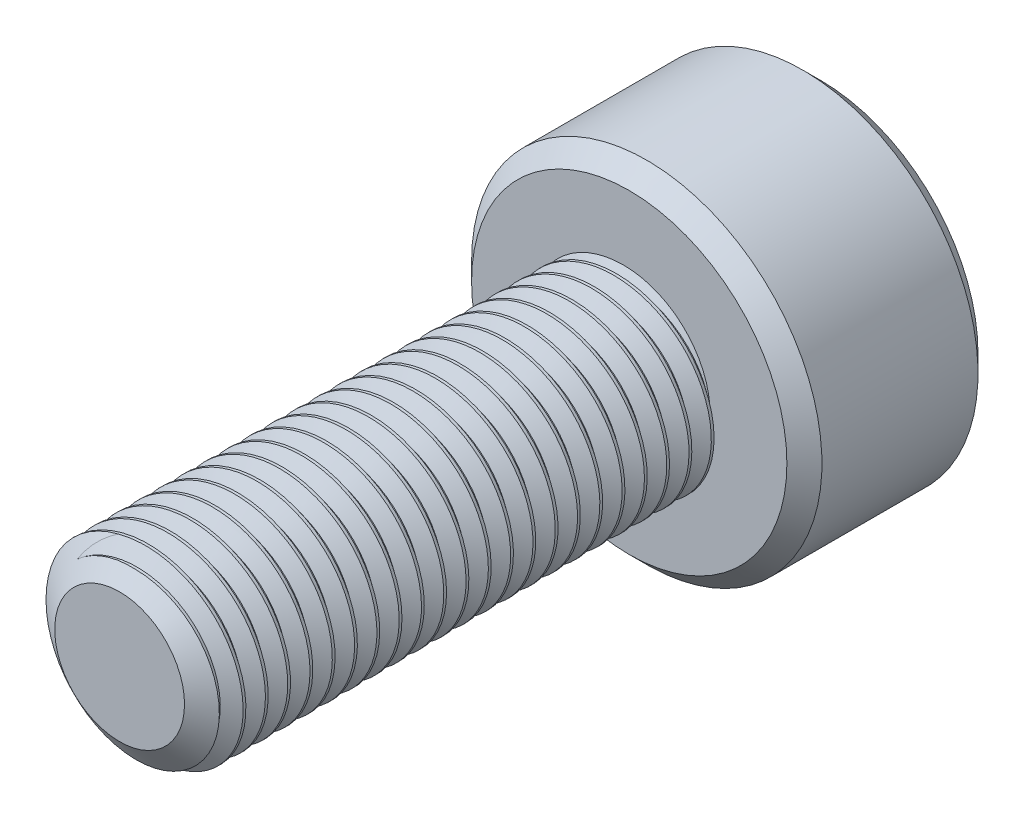
SolidWorks part; units mm, degrees
other "DetailItem1"
ref_plane "Front Plane" through (0, 0, 0) normal (0, 0, 1) x (1, 0, 0)
ref_plane "Top Plane" through (0, 0, 0) normal (0, 1, 0) x (1, 0, 0)
ref_plane "Right Plane" through (0, 0, 0) normal (1, 0, 0) x (0, 0, -1)
sketch "Sketch1" plane through (0, 0, 0) normal (0, 0, 1) x (1, 0, 0)
  circle A0 centre (0, 0) radius 1.5
  dimension "OD" = 3
extrude "Extrude1" add sketch "Sketch1" against normal blind 8
sketch "Sketch2" plane through (0, 0, 0) normal (0, 0, 1) x (1, 0, 0)
  circle A0 centre (0, 0) radius 1.5 construction
  circle A1 centre (0, 0) radius 1.5
curve "Helix/Spiral1" pitch 0.35 height 8.35 radius 1.5 centre (0, 0, 0) axis (0, 0, -1) start towards (0, 1, 0) parameters "pitch"=0.35
sketch "Sketch3" plane through (0, 0, 0) normal (1, 0, 0) x (0, 0, -1)
  line L0 (-0.3062, 1.5) -> (-0.175, 1.2727)
  line L1 (-0.175, 1.2727) -> (-0.1313, 1.2727)
  line L2 (-0.1313, 1.2727) -> (0, 1.5)
  line L3 (-0.3062, 1.5) -> (0, 1.5)
  line L4 (-0.1531, 1.5) -> (-0.1531, 1.2727) construction
  line L5 (-0.2406, 1.3863) -> (-0.0656, 1.3863) construction
  line L6 (0, 1.5) -> (0, -1.5) construction
  dimension "D1" = 0.0437
  dimension "D2" = 0.175
  dimension "D3" = 60
sweep "Cut-Sweep1" cut profiles "Sketch3" path "Helix/Spiral1" align with end faces yes
sketch "Sketch4" plane through (0, 0, 0) normal (1, 0, 0) x (0, 0, -1)
  line L0 (0.337, 1.5) -> (0, 1.0187)
  line L1 (0, 1.0187) -> (0, 1.5)
  line L2 (0.337, 1.5) -> (0, 1.5)
  line L3 (-0.3062, 1.5) -> (0, 1.5) construction
  line L4 (0, 0) -> (7.0209, 0) construction
  dimension "D1" = 55
  dimension "D2" = 0.254
revolve "Cut-Revolve1" cut sketch "Sketch4" angle 360 about L4
sketch "Sketch6" plane through (0, 0, -8) normal (0, 0, -1) x (-1, 0, 0)
  circle A0 centre (0, 0) radius 2.75
  dimension "head dia" = 5.5
extrude "Extrude2" add sketch "Sketch6" along normal blind 3
sketch "Sketch7" plane through (0, 0, -11) normal (0, 0, -1) x (-1, 0, 0)
  line L1 (0, 1.4434) -> (-1.25, 0.7217)
  line L2 (-1.25, 0.7217) -> (-1.25, -0.7217)
  line L3 (-1.25, -0.7217) -> (0, -1.4434)
  line L4 (0, -1.4434) -> (1.25, -0.7217)
  line L5 (1.25, -0.7217) -> (1.25, 0.7217)
  line L6 (1.25, 0.7217) -> (0, 1.4434)
  circle A0 centre (0, 0) radius 1.25 construction
  dimension "hex dia" = 2.5
extrude "Cut-Extrude1" cut sketch "Sketch7" against normal blind 1.875
sketch "Sketch8" plane through (0, 0, -11) normal (0, 0, -1) x (-1, 0, 0)
  circle A0 centre (0, 0) radius 1.4434
extrude "Cut-Extrude2" cut sketch "Sketch8" against normal through all draft 45
chamfer "Chamfer1" distance 0.275 angle 45 2 edges at (-2.75, 0, -11) (-2.75, 0, -8)
sketch "Sketch10" plane through (0, 0, -8) normal (0, 0, 1) x (1, 0, 0)
  circle A1 centre (0, 0) radius 1.5
  circle A2 centre (0, 0) radius 1.5
  dimension "D1" = 0
ref_plane "Plane1" through (0, 0, -7) normal (0, 0, 1) x (1, 0, 0)
extrude "partial thread" [suppressed] add sketch "Sketch10" along normal up to surface (3 mm away) separate body
chamfer "Chamfer2" [suppressed] distance 0.06 angle 45
combine bodies "Combine1" [suppressed] operation type add bodies to combine 107 108
sketch "Sketch9" plane through (0, 0, 0) normal (1, 0, 0) x (0, 0, -1)
  line L0 (0, 1.5) -> (0, -1.5) construction
  line L1 (0.875, 1.5) -> (0.875, -1.5) construction
  dimension "D1" = 0.875
equation "\"D3@Helix/Spiral1\" = \"screw length@Extrude1\"+\"pitch@Helix/Spiral1\""
equation "\"D1@Sketch3\" = \"pitch@Helix/Spiral1\"*.125"
equation "\"D2@Sketch3\" = \"pitch@Helix/Spiral1\"*.5"
equation "\"D1@Cut-Extrude1\" = \"hex dia@Sketch7\"*.75"
equation "\"D1@Chamfer1\" = \"head dia@Sketch6\"*.05"
equation "\"D1@Sketch9\" = \"pitch@Helix/Spiral1\"*2.5"
equation "\"D1@Chamfer2\"=\"OD@Sketch1\"*.02"
